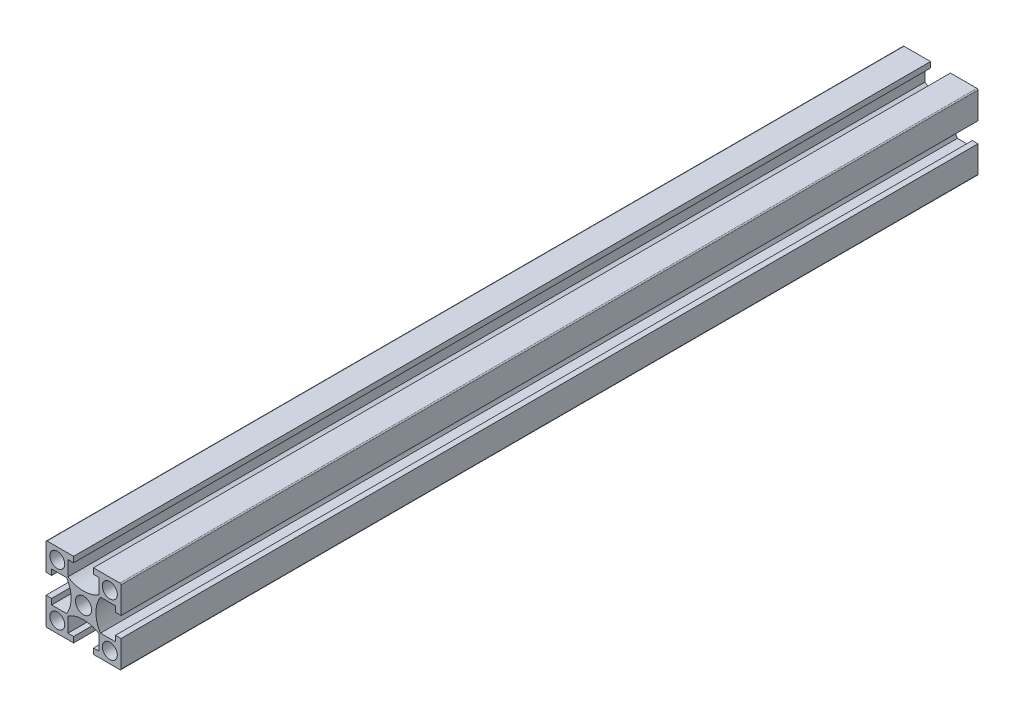
SolidWorks part; units mm, degrees
material "3.0255 (EN-AW 1350A)"
ref_plane "정면" through (0, 0, 0) normal (0, 0, 1) x (1, 0, 0)
ref_plane "윗면" through (0, 0, 0) normal (0, 1, 0) x (1, 0, 0)
ref_plane "우측면" through (0, 0, 0) normal (1, 0, 0) x (0, 0, -1)
sketch "스케치1" plane through (0, 0, 0) normal (0, 0, 1) x (1, 0, 0)
  line L0 (0, 32.0265) -> (0, -31.6588) construction
  line L1 (-10, 10) -> (-10, -10)
  line L2 (-10, 10) -> (10, 10)
  line L3 (-10, 2.65) -> (-8.5, 2.65)
  line L4 (13.6618, 0) -> (-11.6993, 0) construction
  line L5 (-8.5, 2.65) -> (-8.5, 4.15)
  line L6 (-8.5, 4.15) -> (-4.5032, 4.15)
  line L7 (-10, -2.65) -> (-8.5, -2.65)
  line L8 (-8.5, -2.65) -> (-8.5, -4.15)
  line L9 (-8.5, -4.15) -> (-4.5032, -4.15)
  line L10 (-10, -10) -> (10, -10)
  line L11 (10, 10) -> (10, -10)
  circle A0 centre (-7, 7) radius 2
  circle A1 centre (-7, -7) radius 2
  arc A2 (-4.5032, 4.15) -> (-4.5032, -4.15) centre (-11.0587, 0) cw
  circle A3 centre (0, 0) radius 2.15
  circle A4 centre (7, 7) radius 2
  circle A5 centre (7, -7) radius 2
  point P21 (-10, 0)
  point P23 (-3.3, 0)
  point P31 (0, -10)
  point P32 (0, 10)
  dimension "D3" = 4
  dimension "D9" = 6.7
  dimension "D10" = 4.3
  dimension "D11" = 7.7587
  dimension "D1" = 20
  dimension "D2" = 20
  dimension "D4" = 14
  dimension "D5" = 14
  dimension "D6" = 5.3
  dimension "D7" = 8.3
  dimension "D8" = 1.5
extrude "보스-돌출1" add sketch "스케치1" along normal blind 345 contours A0 | A4 | A3 | A5 | A1 | A2 L6 L5 L3 L1 L7 L8 L9 | L2 L11 L10 L1 region at (-6.6069, 0, 0) region at (-7, 7, 0) region at (-7, -7, 0) region at (0, 0, 0) region at (7, 7, 0) region at (7, -7, 0)
extrude "컷-돌출1" cut sketch "스케치1<3>" along normal up to next contours A2 L6 L5 L3 L1 L7 L8 L9 region at (-6.6069, 0, 0)
sketch "스케치1<3>" plane through (0, 0, 0) normal (0, 0, 1) x (1, 0, 0) same geometry as "스케치1"
pattern_circular "원형 패턴1" count 4 over 360 about axis through (0, 0, 345) along (0, 0, -1) of "컷-돌출1" reverse direction yes
fillet "필렛1" radius 0.3 4 edges at (10, -10, 172.5) (-10, -10, 172.5) (-10, 10, 172.5) (10, 10, 172.5)
sketch "스케치2" plane through (0, 0, 0) normal (1, 0, 0) x (0, 0, -1)
  circle A0 centre (-25, 0) radius 2.5
  dimension "D1" = 5
  dimension "D2" = 25
extrude "컷-돌출2" cut sketch "스케치2" against normal through all both and the other way through all
sketch "스케치4" plane through (0, 10, 0) normal (0, 1, 0) x (1, 0, 0)
  line L0 (0, -11) -> (0, 11) construction
  line L1 (2.65, -345) -> (9.7, -345) construction
  line L3 (-2.65, -106.62) -> (2.65, -106.62) construction
  line L4 (-2.65, -345) -> (-2.65, 0) construction
  line L5 (2.65, -345) -> (2.65, 0) construction
  line L6 (2.65, 0) -> (9.7, 0) construction
  circle A4 centre (0, -303) radius 2.15
  dimension "D3" = 106.62
  dimension "D5" = 42
extrude "컷-돌출3" cut sketch "스케치4" against normal through all
sketch "스케치6" plane through (0, 10, 0) normal (0, 1, 0) x (1, 0, 0)
  line L0 (0, -11) -> (0, 11) construction
  line L1 (4.15, 0) -> (-4.15, 0) construction
  line L3 (-9.7, 0) -> (-2.65, 0) construction
  circle A0 centre (0, -236.9) radius 2.15
  circle A1 centre (0, -184.9) radius 2.15
  circle A2 centre (0, -10.15) radius 1.9797
  circle A3 centre (0, -62.15) radius 2.15
  dimension "D1" = 184.9
  dimension "D2" = 236.9
  dimension "D4" = 52
  dimension "D3" = 10.15
extrude "컷-돌출4" cut sketch "스케치6" against normal through all
sketch "스케치7" plane through (0, 10, 0) normal (0, 1, 0) x (1, 0, 0)
  line L0 (-10, -116.62) -> (10, -116.62)
  line L1 (-10, -345) -> (-10, 0) construction
  line L2 (10, 0) -> (10, -345) construction
  line L6 (-10, -116.62) -> (-10, 0)
  line L7 (-10, 0) -> (10, 0)
  line L8 (10, 0) -> (10, -116.62)
extrude "컷-돌출5" cut sketch "스케치7" against normal through all
sketch "스케치8" plane through (0, 10, 0) normal (0, 1, 0) x (1, 0, 0)
  line L0 (9.7, -345) -> (2.65, -345)
